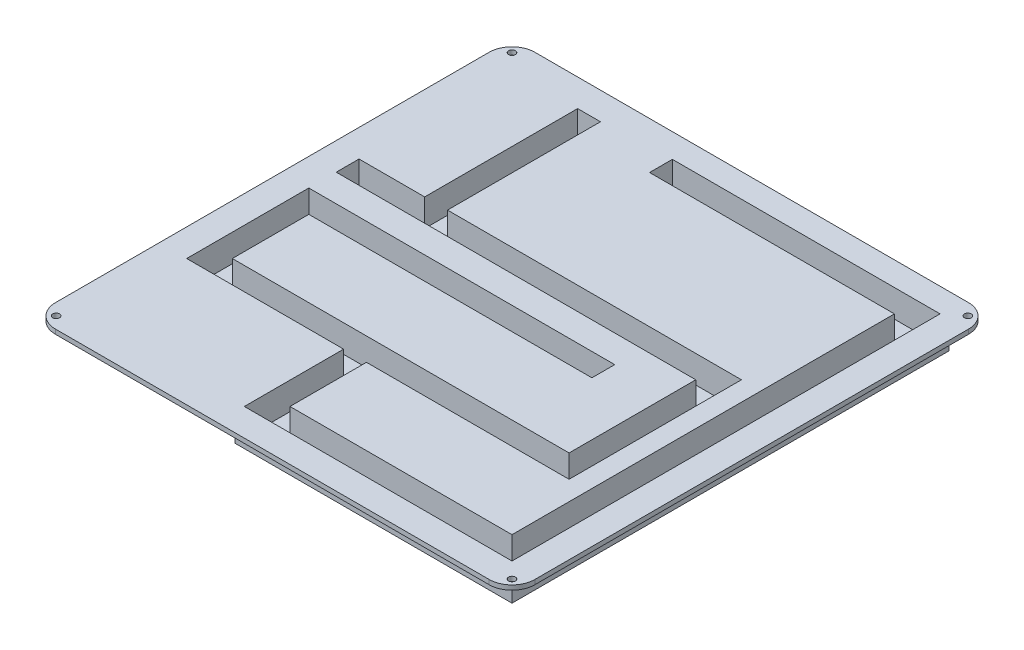
SolidWorks part; units mm, degrees
ref_plane "Front Plane" through (0, 0, 0) normal (0, 0, 1) x (1, 0, 0)
ref_plane "Top Plane" through (0, 0, 0) normal (0, 1, 0) x (1, 0, 0)
ref_plane "Right Plane" through (0, 0, 0) normal (1, 0, 0) x (0, 0, -1)
sketch "Sketch1" plane through (0, 0, 0) normal (0, 1, 0) x (1, 0, 0)
  line L0 (-101, -101) -> (-101, 101)
  line L5 (-105, -105) -> (105, -105)
  line L6 (-105, -105) -> (-105, 105)
  line L7 (-105, 105) -> (105, 105)
  line L8 (105, -105) -> (105, 105)
  line L9 (-101, 101) -> (101, 101)
  line L10 (101, -101) -> (101, 101)
  line L11 (-101, -101) -> (101, -101)
  line L12 (-101, 101) -> (-99.8333, 99.8333) construction
  line L13 (-55, 0) -> (55, 0) construction
  line L14 (-101, -101) -> (-99.8333, -99.8333) construction
  line L15 (0, -55) -> (0, 55) construction
  line L16 (101, -101) -> (99.8333, -99.8333) construction
  line L17 (101, 101) -> (99.8333, 99.8333) construction
  circle A1 centre (-99.8333, 99.8333) radius 1.5
  circle A2 centre (-99.8333, -99.8333) radius 1.5
  circle A3 centre (99.8333, -99.8333) radius 1.5
  circle A4 centre (99.8333, 99.8333) radius 1.5
  point P0 (0, 0)
  point P6 (-105, 0)
  point P7 (0, 105)
  dimension "D3" = 4
  dimension "D4" = 3
  dimension "D1" = 210
  dimension "D2" = 210
  dimension "D5" = 1.65
  dimension "D6" = 45
extrude "MainExtrude" add sketch "Sketch1" along normal blind 2 contours L6 L5 L8 L7
extrude "ScrewHoles" cut sketch "Sketch1<6>" along normal up to surface (2 mm away) contours A1 | A2 | A3 | A4 up to face at (0, 2, 0)
sketch "Sketch1<6>" plane through (0, 0, 0) normal (0, 1, 0) x (1, 0, 0) same geometry as "Sketch1"
fillet "RoundedCorners" radius 10 4 edges at (-105, 1, -105) (-105, 1, 105) (105, 1, -105) (105, 1, 105)
sketch "Sketch3" plane through (0, 0, 0) normal (0, 1, 0) x (1, 0, 0)
  line L24 (-59.25, 93) -> (-59.25, 26) construction
  line L25 (-64.25, 93) -> (-64.25, 26)
  line L58 (-93, 21) -> (69.5, 21) construction
  line L59 (69.5, 21) -> (69.5, -44.5) construction
  line L60 (69.5, -44.5) -> (-88, -44.5) construction
  line L61 (-88, -44.5) -> (-88, -1) construction
  line L62 (-88, -1) -> (41, -1) construction
  line L63 (-19.25, -49.5) -> (-19.25, -88) construction
  line L64 (-19.25, -88) -> (88, -88) construction
  line L65 (88, -88) -> (88, 89.5) construction
  line L66 (88, 89.5) -> (-24.25, 89.5) construction
  line L68 (-93, 16) -> (64.5, 16)
  line L69 (64.5, 16) -> (64.5, -39.5)
  line L70 (64.5, -39.5) -> (-83, -39.5)
  line L71 (-83, -39.5) -> (-83, -6)
  line L72 (-83, -6) -> (41, -6)
  line L73 (-24.25, -49.5) -> (-24.25, -93)
  line L74 (-24.25, -93) -> (93, -93)
  line L75 (93, -93) -> (93, 94.5)
  line L76 (93, 94.5) -> (-24.25, 94.5)
  line L77 (-54.25, 93) -> (-54.25, 26)
  line L78 (-93, 26) -> (-64.25, 26)
  line L79 (74.5, 26) -> (74.5, -49.5)
  line L80 (74.5, -49.5) -> (-14.25, -49.5)
  line L81 (-93, -49.5) -> (-93, 4)
  line L82 (-93, 4) -> (41, 4)
  line L83 (-14.25, -49.5) -> (-14.25, -83)
  line L84 (-14.25, -83) -> (83, -83)
  line L85 (83, -83) -> (83, 84.5)
  line L86 (83, 84.5) -> (-24.25, 84.5)
  line L87 (-64.25, 93) -> (-54.25, 93)
  line L89 (-93, 16) -> (-93, 26)
  line L90 (41, -6) -> (41, 4)
  line L92 (-24.25, 94.5) -> (-24.25, 84.5)
  line L93 (-54.25, 93) -> (-54.25, 39.3434) construction
  line L94 (-59.25, 93) -> (-59.25, 39.3434) construction
  line L95 (-64.25, 93) -> (-64.25, 39.3434) construction
  line L96 (-14.25, 9.5948) -> (-14.25, -83) construction
  line L97 (-19.25, 9.5948) -> (-19.25, -88) construction
  line L98 (-24.25, 9.5948) -> (-24.25, -93) construction
  line L99 (-24.25, -49.5) -> (-93, -49.5)
  line L100 (74.5, -49.5) -> (-93, -49.5) construction
  line L101 (-54.25, 26) -> (74.5, 26)
  line L102 (-93, 26) -> (74.5, 26) construction
  line L106 (-105, -95) -> (-105, 95) construction
  line L107 (-95, -105) -> (95, -105) construction
  line L108 (-95, 105) -> (95, 105) construction
  line L109 (105, -95) -> (105, 95) construction
  dimension "D1" = 5
  dimension "D2" = 5
  dimension "D3" = 12
  dimension "D4" = 12
  dimension "D5" = 12
  dimension "D6" = 12
  dimension "D7" = 67
  dimension "D8" = 167.5
  dimension "D9" = 134
  dimension "D11" = 117.25
  dimension "D13" = 33.5
  dimension "D14" = 117.25
  dimension "D10" = 33.5
  dimension "D12" = 167.5
  dimension "D15" = 30
  dimension "D17" = 167.5
  dimension "D16" = 55.5
extrude "Trench" cut sketch "Sketch3" along normal blind 12
sketch "Sketch7" plane through (0, 0, 0) normal (0, -1, 0) x (1, 0, 0)
  line L0 (-66.25, -95) -> (-52.25, -95)
  line L1 (-52.25, -95) -> (-52.25, -28)
  line L2 (-52.25, -28) -> (76.5, -28)
  line L3 (76.5, -28) -> (76.5, 51.5)
  line L5 (76.5, 51.5) -> (-12.25, 51.5)
  line L6 (-12.25, 51.5) -> (-12.25, 81)
  line L7 (-12.25, 81) -> (81, 81)
  line L12 (81, 81) -> (81, -82.5)
  line L13 (81, -82.5) -> (-26.25, -82.5)
  line L14 (-26.25, -82.5) -> (-26.25, -96.5)
  line L15 (-26.25, -96.5) -> (95, -96.5)
  line L16 (95, -96.5) -> (95, 95)
  line L17 (95, 95) -> (-26.25, 95)
  line L18 (-26.25, 95) -> (-26.25, 51.5)
  line L19 (-26.25, 51.5) -> (-95, 51.5)
  line L20 (-95, 51.5) -> (-95, -6)
  line L21 (-95, -6) -> (43, -6)
  line L22 (43, -6) -> (43, 8)
  line L23 (43, 8) -> (-81, 8)
  line L24 (-81, 8) -> (-81, 37.5)
  line L25 (-81, 37.5) -> (62.5, 37.5)
  line L26 (62.5, 37.5) -> (62.5, -14)
  line L27 (62.5, -14) -> (-95, -14)
  line L28 (-95, -14) -> (-95, -28)
  line L29 (-95, -28) -> (-66.25, -28)
  line L30 (-66.25, -28) -> (-66.25, -95)
  line L31 (-64.25, -93) -> (-54.25, -93)
  line L32 (-64.25, -26) -> (-64.25, -93)
  line L33 (-93, -26) -> (-64.25, -26)
  line L34 (-93, -16) -> (-93, -26)
  line L35 (64.5, -16) -> (-93, -16)
  line L36 (64.5, 39.5) -> (64.5, -16)
  line L37 (-83, 39.5) -> (64.5, 39.5)
  line L38 (-83, 6) -> (-83, 39.5)
  line L39 (41, 6) -> (-83, 6)
  line L40 (41, -4) -> (41, 6)
  line L41 (-93, -4) -> (41, -4)
  line L42 (-93, 49.5) -> (-93, -4)
  line L43 (-24.25, 49.5) -> (-93, 49.5)
  line L44 (-24.25, 93) -> (-24.25, 49.5)
  line L45 (93, 93) -> (-24.25, 93)
  line L46 (93, -94.5) -> (93, 93)
  line L47 (-24.25, -94.5) -> (93, -94.5)
  line L48 (-24.25, -84.5) -> (-24.25, -94.5)
  line L49 (83, -84.5) -> (-24.25, -84.5)
  line L50 (83, 83) -> (83, -84.5)
  line L51 (-14.25, 83) -> (83, 83)
  line L52 (-14.25, 49.5) -> (-14.25, 83)
  line L53 (74.5, 49.5) -> (-14.25, 49.5)
  line L54 (74.5, -26) -> (74.5, 49.5)
  line L55 (-54.25, -26) -> (74.5, -26)
  line L56 (-54.25, -93) -> (-54.25, -26)
  line L57 (-64.25, -93) -> (-54.25, -93)
  line L58 (-64.25, -26) -> (-64.25, -93)
  line L59 (-93, -26) -> (-64.25, -26)
  line L60 (-93, -16) -> (-93, -26)
  line L61 (64.5, -16) -> (-93, -16)
  line L62 (64.5, 39.5) -> (64.5, -16)
  line L63 (-83, 39.5) -> (64.5, 39.5)
  line L64 (-83, 6) -> (-83, 39.5)
  line L65 (41, 6) -> (-83, 6)
  line L66 (41, -4) -> (41, 6)
  line L67 (-93, -4) -> (41, -4)
  line L68 (-93, 49.5) -> (-93, -4)
  line L69 (-24.25, 49.5) -> (-93, 49.5)
  line L70 (-24.25, 93) -> (-24.25, 49.5)
  line L71 (93, 93) -> (-24.25, 93)
  line L72 (93, -94.5) -> (93, 93)
  line L73 (-24.25, -94.5) -> (93, -94.5)
  line L74 (-24.25, -84.5) -> (-24.25, -94.5)
  line L75 (83, -84.5) -> (-24.25, -84.5)
  line L76 (83, 83) -> (83, -84.5)
  line L77 (-14.25, 83) -> (83, 83)
  line L78 (-14.25, 49.5) -> (-14.25, 83)
  line L79 (74.5, 49.5) -> (-14.25, 49.5)
  line L80 (74.5, -26) -> (74.5, 49.5)
  line L81 (-54.25, -26) -> (74.5, -26)
  line L82 (-54.25, -93) -> (-54.25, -26)
  dimension "D1" = 0
  dimension "D2" = 2
extrude "Boss-Extrude3" add sketch "Sketch7" along normal blind 10
sketch "Sketch8" plane through (0, -10, 0) normal (0, -1, 0) x (1, 0, 0)
  line L26 (-66.25, -28) -> (-66.25, -95)
  line L27 (-66.25, -95) -> (-52.25, -95)
  line L28 (-52.25, -95) -> (-52.25, -28)
  line L29 (-52.25, -28) -> (76.5, -28)
  line L30 (76.5, -28) -> (76.5, 51.5)
  line L31 (76.5, 51.5) -> (-12.25, 51.5)
  line L32 (-12.25, 51.5) -> (-12.25, 81)
  line L33 (-12.25, 81) -> (81, 81)
  line L34 (81, 81) -> (81, -82.5)
  line L35 (81, -82.5) -> (-26.25, -82.5)
  line L36 (-26.25, -82.5) -> (-26.25, -96.5)
  line L37 (-26.25, -96.5) -> (95, -96.5)
  line L38 (95, -96.5) -> (95, 95)
  line L39 (95, 95) -> (-26.25, 95)
  line L40 (-26.25, 95) -> (-26.25, 51.5)
  line L41 (-26.25, 51.5) -> (-95, 51.5)
  line L42 (-95, 51.5) -> (-95, -6)
  line L43 (-95, -6) -> (43, -6)
  line L44 (43, -6) -> (43, 8)
  line L45 (43, 8) -> (-81, 8)
  line L46 (-81, 8) -> (-81, 37.5)
  line L47 (-81, 37.5) -> (62.5, 37.5)
  line L48 (62.5, 37.5) -> (62.5, -14)
  line L49 (62.5, -14) -> (-95, -14)
  line L50 (-95, -14) -> (-95, -28)
  line L51 (-95, -28) -> (-66.25, -28)
  line L52 (-66.25, -28) -> (-66.25, -95)
  line L53 (-66.25, -95) -> (-52.25, -95)
  line L54 (-52.25, -95) -> (-52.25, -28)
  line L55 (-52.25, -28) -> (76.5, -28)
  line L56 (76.5, -28) -> (76.5, 51.5)
  line L57 (76.5, 51.5) -> (-12.25, 51.5)
  line L58 (-12.25, 51.5) -> (-12.25, 81)
  line L59 (-12.25, 81) -> (81, 81)
  line L60 (81, 81) -> (81, -82.5)
  line L61 (81, -82.5) -> (-26.25, -82.5)
  line L62 (-26.25, -82.5) -> (-26.25, -96.5)
  line L63 (-26.25, -96.5) -> (95, -96.5)
  line L64 (95, -96.5) -> (95, 95)
  line L65 (95, 95) -> (-26.25, 95)
  line L66 (-26.25, 95) -> (-26.25, 51.5)
  line L67 (-26.25, 51.5) -> (-95, 51.5)
  line L68 (-95, 51.5) -> (-95, -6)
  line L69 (-95, -6) -> (43, -6)
  line L70 (43, -6) -> (43, 8)
  line L71 (43, 8) -> (-81, 8)
  line L72 (-81, 8) -> (-81, 37.5)
  line L73 (-81, 37.5) -> (62.5, 37.5)
  line L74 (62.5, 37.5) -> (62.5, -14)
  line L75 (62.5, -14) -> (-95, -14)
  line L76 (-95, -14) -> (-95, -28)
  line L77 (-95, -28) -> (-66.25, -28)
  dimension "D1" = 0
extrude "Boss-Extrude4" add sketch "Sketch8" along normal blind 2
